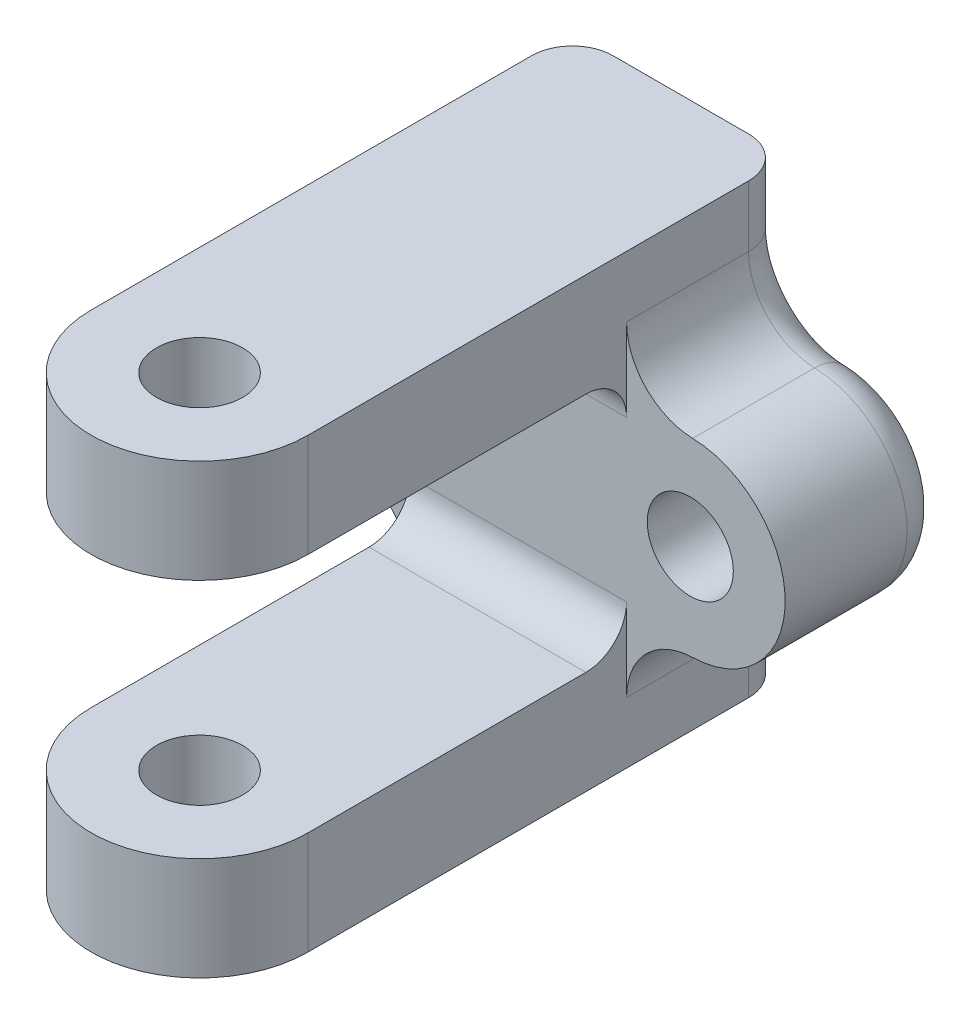
SolidWorks part; units mm, degrees
material "7075-T6 (SN)"
ref_plane "Front Plane" through (0, 0, 0) normal (0, 0, 1) x (1, 0, 0)
ref_plane "Top Plane" through (0, 0, 0) normal (0, 1, 0) x (1, 0, 0)
ref_plane "Right Plane" through (0, 0, 0) normal (1, 0, 0) x (0, 0, -1)
sketch "Sketch1" plane through (0, 0, 0) normal (0, 0, 1) x (1, 0, 0)
  line L0 (12.7, 0) -> (-12.7, 0) construction
  line L1 (-20.7, -16.51) -> (20.7, -16.51)
  line L2 (-20.7, -16.51) -> (-20.7, 16.51)
  line L3 (-20.7, 16.51) -> (20.7, 16.51)
  line L4 (20.7, -16.51) -> (20.7, 16.51)
  line L5 (-20.7, -16.51) -> (20.7, 16.51) construction
  line L6 (-20.7, 16.51) -> (20.7, -16.51) construction
  circle A0 centre (12.7, 0) radius 3.175
  circle A1 centre (-12.7, 0) radius 3.175
  point P0 (0, 0)
  dimension "D1" = 6.35
  dimension "D2" = 25.4
  dimension "D3" = 8
  dimension "D4" = 16.51
extrude "Boss-Extrude1" add sketch "Sketch1" along normal blind 12
sketch "Sketch2" plane through (0, 0, 12) normal (0, 0, 1) x (1, 0, 0)
  line L0 (-12.7, 0) -> (12.7, 0) construction
  line L2 (-20.7, 8.89) -> (20.7, 8.89)
  line L3 (-20.7, 8.89) -> (-20.7, 16.51)
  line L4 (-20.7, 16.51) -> (20.7, 16.51)
  line L5 (20.7, 8.89) -> (20.7, 16.51)
  line L6 (-20.7, 8.89) -> (20.7, 16.51) construction
  line L7 (-20.7, 16.51) -> (20.7, 8.89) construction
  line L8 (-20.7, 16.51) -> (-20.7, -16.51) construction
  line L9 (20.7, -8.89) -> (20.7, -16.51)
  line L10 (-20.7, -8.89) -> (-20.7, -16.51)
  line L11 (-20.7, -16.51) -> (20.7, -8.89) construction
  line L12 (-20.7, -8.89) -> (20.7, -16.51) construction
  line L13 (-20.7, -8.89) -> (20.7, -8.89)
  line L14 (-20.7, -16.51) -> (20.7, -16.51)
  circle A0 centre (-12.7, 0) radius 3.175 construction
  circle A1 centre (12.7, 0) radius 3.175 construction
  point P6 (0, 12.7)
  point P21 (0, -12.7)
  dimension "D1" = 17.78
extrude "Boss-Extrude2" add sketch "Sketch2" along normal blind 53
sketch "Sketch3" plane through (0, 0, 0) normal (0, 1, 0) x (1, 0, 0)
  point P0 (0, -35.5)
  dimension "D1" = 35.5
ref_point "UBJ Point"
sketch "Sketch4" plane through (0, 0, 0) normal (0, 1, 0) x (1, 0, 0)
  circle A0 centre (0, -35.5) radius 3.175
  dimension "D1" = 6.35
extrude "Cut-Extrude1" cut sketch "Sketch4" against normal up to surface and the other way up to surface up to face at (0, -16.51, 32.5) other way up to face at (0, 16.51, 32.5)
sketch "Sketch5" plane through (0, 0, 0) normal (0, 1, 0) x (1, 0, 0)
  line L0 (20.7, -12) -> (8.3595, -39.2814)
  line L1 (-8.3595, -39.2814) -> (-20.7, -12)
  line L4 (20.7, 0) -> (-20.7, 0)
  line L5 (-20.7, 0) -> (-20.7, -65)
  line L6 (-20.7, -65) -> (20.7, -65)
  line L7 (20.7, -65) -> (20.7, 0)
  line L9 (-20.7, -12) -> (-20.7, -65)
  line L10 (-20.7, -65) -> (20.7, -65)
  line L11 (20.7, -65) -> (20.7, -12)
  line L12 (20.7, -12) -> (-20.7, -12)
  line L13 (20.7, -65) -> (20.7, -12)
  line L14 (-20.7, -65) -> (20.7, -65)
  line L15 (-20.7, -12) -> (-20.7, -65)
  line L17 (20.7, -65) -> (20.7, -12)
  line L18 (-20.7, -65) -> (20.7, -65)
  line L19 (-20.7, -12) -> (-20.7, -65)
  arc A0 (-8.3595, -39.2814) -> (8.3595, -39.2814) centre (0, -35.5) ccw
  circle A1 centre (0, -35.5) radius 3.175 construction
  circle A2 centre (0, -35.5) radius 3.175 construction
  dimension "D3" = 6
  dimension "D1" = 0
  dimension "D2" = 0
extrude "Cut-Extrude2" [suppressed] cut sketch "Sketch5" against normal up to surface and the other way up to surface contours A0 L1 L9 L10 L11 L0 up to face at (0, -16.51, 38.675) other way up to face at (0, 16.51, 32.325)
sketch "Sketch6" plane through (0, 0, 0) normal (0, 1, 0) x (1, 0, 0)
  line L0 (-8, -35.5) -> (-8, -20)
  line L1 (8, -35.5) -> (8, -20)
  line L2 (-16, -12) -> (-20.7, -12)
  line L3 (-8, -20) -> (-8, -12)
  line L4 (20.7, -12) -> (-20.7, -12)
  line L5 (-20.7, -12) -> (-20.7, -65)
  line L6 (-20.7, -65) -> (20.7, -65)
  line L7 (20.7, -65) -> (20.7, -12)
  line L8 (20.7, -12) -> (16, -12)
  line L9 (-20.7, -12) -> (-20.7, -65)
  line L10 (-20.7, -65) -> (20.7, -65)
  line L11 (20.7, -65) -> (20.7, -12)
  line L12 (-8, -12) -> (-16, -12)
  line L13 (8, -20) -> (8, -12)
  line L14 (8, -12) -> (16, -12)
  arc A0 (-8, -35.5) -> (8, -35.5) centre (0, -35.5) ccw
  circle A1 centre (0, -35.5) radius 3.175 construction
  arc A2 (-8, -20) -> (-16, -12) centre (-16, -20) ccw construction
  arc A3 (8, -20) -> (16, -12) centre (16, -20) cw construction
  dimension "D2" = 8
  dimension "D3" = 8
  dimension "D1" = 0
extrude "Cut-Extrude3" cut sketch "Sketch6" against normal up to surface and the other way up to surface up to face at (0, -16.51, 38.675) other way up to face at (0, 16.51, 32.325)
fillet "Fillet1" [suppressed] radius 12.7
sketch "Sketch7" plane through (0, 0, 0) normal (0, 0, 1) x (1, 0, 0)
  line L0 (-12.7, 7) -> (-8, 7)
  line L1 (-12.7, -7) -> (-8, -7)
  line L2 (-8, 16.51) -> (-8, 7)
  line L3 (-8, -16.51) -> (-8, -7)
  line L4 (0, 10.3988) -> (0, -8.4154) construction
  line L5 (8, -16.51) -> (8, -7)
  line L6 (20.7, -16.51) -> (8, -16.51)
  line L7 (20.7, 16.51) -> (20.7, -16.51)
  line L8 (8, 16.51) -> (20.7, 16.51)
  line L9 (8, 16.51) -> (8, 7)
  line L10 (12.7, 7) -> (8, 7)
  line L11 (12.7, -7) -> (8, -7)
  line L12 (8, 8.89) -> (-8, 8.89)
  line L13 (-8, 8.89) -> (-8, 16.51)
  line L14 (-8, 16.51) -> (-20.7, 16.51)
  line L15 (-20.7, 16.51) -> (-20.7, -16.51)
  line L16 (-20.7, -16.51) -> (-8, -16.51)
  line L17 (-8, -16.51) -> (-8, -8.89)
  line L18 (-8, -8.89) -> (8, -8.89)
  line L19 (8, -8.89) -> (8, -16.51)
  line L20 (8, -16.51) -> (20.7, -16.51)
  line L21 (20.7, -16.51) -> (20.7, 16.51)
  line L22 (20.7, 16.51) -> (8, 16.51)
  line L23 (8, 16.51) -> (8, 8.89)
  line L26 (-8, 16.51) -> (-20.7, 16.51)
  line L27 (-20.7, 16.51) -> (-20.7, -16.51)
  line L28 (-20.7, -16.51) -> (-8, -16.51)
  line L32 (8, -16.51) -> (20.7, -16.51)
  line L33 (20.7, -16.51) -> (20.7, 16.51)
  line L34 (20.7, 16.51) -> (8, 16.51)
  line L36 (-8, 8.89) -> (8, 8.89) construction
  line L37 (8, -8.89) -> (-8, -8.89) construction
  line L38 (-8, 8.89) -> (8, 8.89)
  line L39 (8, -8.89) -> (-8, -8.89)
  arc A0 (-12.7, 7) -> (-12.7, -7) centre (-12.7, 0) ccw
  circle A1 centre (-12.7, 0) radius 3.175 construction
  arc A2 (12.7, 7) -> (12.7, -7) centre (12.7, 0) cw
  dimension "D2" = 7
  dimension "D1" = 0
extrude "Cut-Extrude4" cut sketch "Sketch7" along normal up to surface (12 mm away) contours A0 L0 L2 L26 L27 L28 L3 L1 | L10 A2 L11 L5 L6 L7 L8 L9 region at (-20.0538, 0, 0) region at (8.3538, 12.7, 0) up to face at (0, 0, 12)
fillet "Fillet2" radius 5 4 edges at (8, -7, 6) (8, 7, 6) (-8, 7, 6) (-8, -7, 6)
fillet "Fillet3" radius 3 2 edges at (0, 8.89, 12) (0, -8.89, 12)
fillet "Fillet4" radius 3 10 edges at (-8, -14.2531, 0) (-9.4205, -8.5052, 0) (-19.7, 0, 0) (-8, 14.2531, 0) (8, 14.2531, 0) (9.4205, 8.5052, 0) (8, -14.2531, 0) (9.4205, -8.5052, 0) (-9.4205, 8.5052, 0) (19.7, 0, 0)
